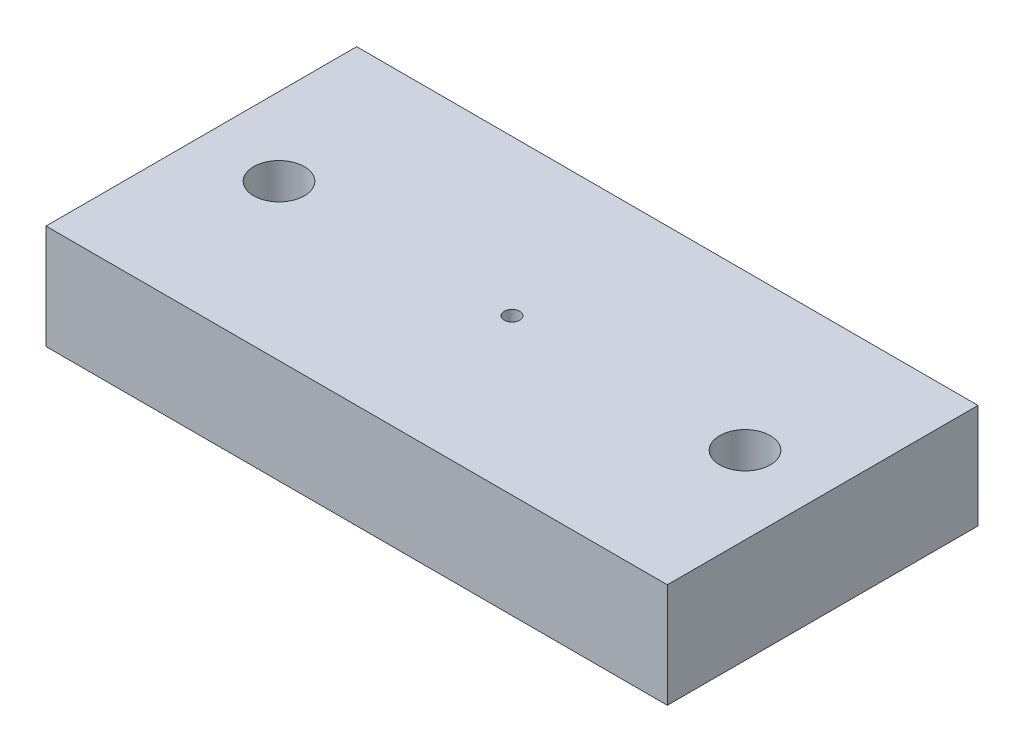
SolidWorks part; units mm, degrees
ref_plane "Front Plane" through (0, 0, 0) normal (0, 0, 1) x (1, 0, 0)
ref_plane "Top Plane" through (0, 0, 0) normal (0, 1, 0) x (1, 0, 0)
ref_plane "Right Plane" through (0, 0, 0) normal (1, 0, 0) x (0, 0, -1)
sketch "Sketch1" plane through (0, 0, 0) normal (0, 1, 0) x (1, 0, 0)
  line L1 (-20, -10) -> (20, -10)
  line L2 (-20, -10) -> (-20, 10)
  line L3 (-20, 10) -> (20, 10)
  line L4 (20, -10) -> (20, 10)
  line L5 (-20, -10) -> (20, 10) construction
  line L6 (-20, 10) -> (20, -10) construction
  point P0 (0, 0)
extrude "Boss-Extrude1" add sketch "Sketch1" along normal blind 6.72
sketch "Sketch2" plane through (0, 6.72, 0) normal (0, 1, 0) x (1, 0, 0)
  circle A0 centre (0, 0) radius 0.5
extrude "Cut-Extrude1" cut sketch "Sketch2" against normal blind 6.72
hole_wizard "CBORE for #4 Pan Head Machine Screw3" positions "3DSketch4" profile "Sketch9" counterbore size "#4" standard "ANSI Inch" end condition through all
sketch3d "3DSketch4"
  point P0 (-15, 0, 0)
sketch "Sketch9" plane through (-15, 0, 0) normal (1, 0, 0) x (0, 0, -1)
  line L0 (0, 0) -> (0, 6.72)
  line L1 (0, 6.72) -> (1.6319, 6.72)
  line L3 (1.6319, 6.72) -> (1.632, 2.032)
  line L4 (3.175, 2.032) -> (1.632, 2.032)
  line L5 (3.175, 2.032) -> (3.175, 0.635)
  line L6 (3.175, 0.635) -> (3.81, 0)
  line L7 (3.81, 0) -> (0, 0)
  line L8 (-3.175, 0.635) -> (-3.81, 0) construction
  line L11 (0, -6.35) -> (0, 107.95) construction
  dimension "Thru Hole Dia." = 3.2639
  dimension "Thru Hole Depth" = 6.72
  dimension "C'Bore Dia." = 6.35
  dimension "C'Bore Depth" = 2.032
  dimension "Near C'Sink Dia." = 7.62
  dimension "Near C'Sink Angle" = 90
sketch "Sketch11" plane through (0, 0, 0) normal (0, -1, 0) x (1, 0, 0)
  line L0 (-20, 0) -> (20, 0) construction
  line L1 (-20, -10) -> (-20, 10) construction
  line L2 (20, 10) -> (20, -10) construction
pattern_linear "LPattern1" count 2 spacing 30 along (1, 0, 0) of "CBORE for #4 Pan Head Machine Screw3"
sketch "Sketch12" plane through (0, 0, 0) normal (0, -1, 0) x (1, 0, 0)
  circle A0 centre (0, 0) radius 4
  circle A1 centre (0, 0) radius 5.05
extrude "Cut-Extrude2" cut sketch "Sketch12" against normal blind 4.72
sketch "Sketch13" plane through (0, 0, 0) normal (0, -1, 0) x (1, 0, 0)
  line L1 (-2.5, 1.75) -> (2.5, 1.75)
  line L2 (-2.5, 1.75) -> (-2.5, -1.75)
  line L3 (-2.5, -1.75) -> (2.5, -1.75)
  line L4 (2.5, 1.75) -> (2.5, -1.75)
  line L5 (-2.5, 1.75) -> (2.5, -1.75) construction
  line L6 (-2.5, -1.75) -> (2.5, 1.75) construction
extrude "Cut-Extrude3" cut sketch "Sketch13" against normal blind 0.5
